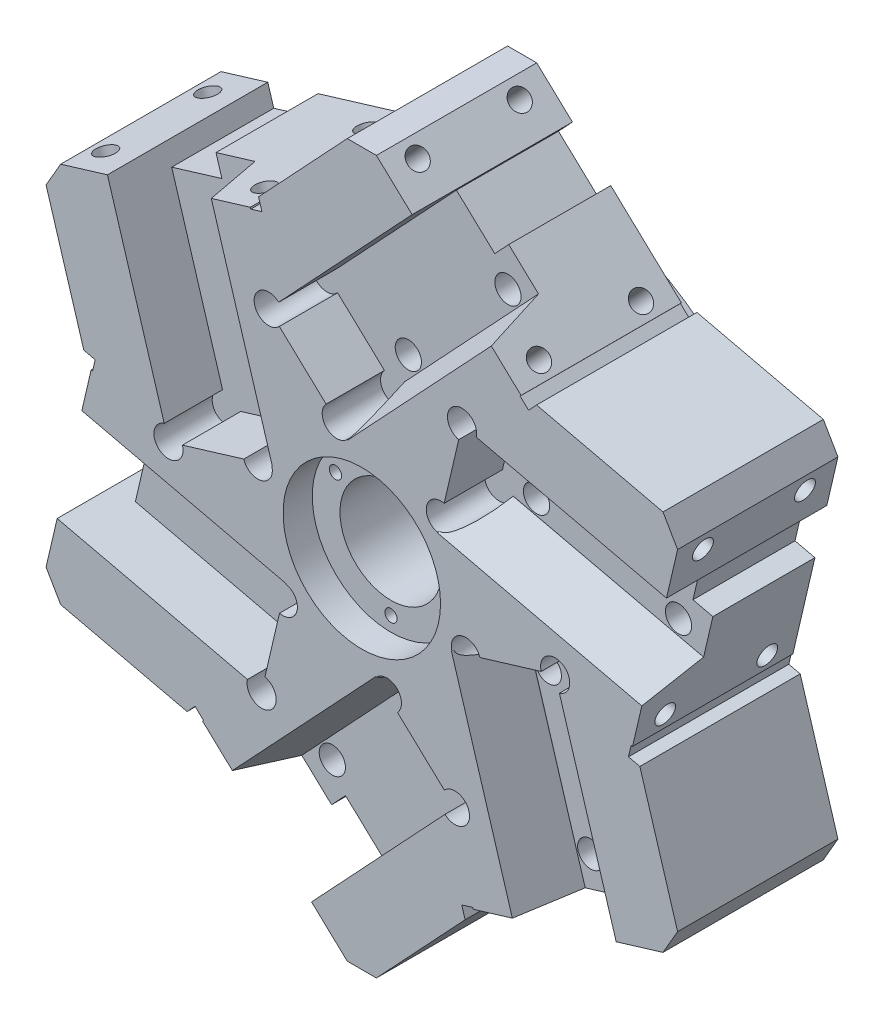
SolidWorks part; units mm, degrees
material "201 Annealed Stainless Steel (SS)"
ref_plane "Front" through (0, 0, 0) normal (0, 0, 1) x (1, 0, 0)
ref_plane "Top" through (0, 0, 0) normal (0, 1, 0) x (1, 0, 0)
ref_plane "Right" through (0, 0, 0) normal (1, 0, 0) x (0, 0, -1)
sketch "Sketch3" plane through (0, 0, 0) normal (0, 0, 1) x (1, 0, 0)
  line L0 (0, 0) -> (-108.311, 0) construction
  line L1 (-5, 122.18) -> (-108.311, 62.5334)
  line L2 (-108.311, 62.5334) -> (-108.311, -62.5334)
  line L3 (-108.311, -62.5334) -> (-5, -122.18)
  line L4 (5, -122.18) -> (103.311, -65.4201)
  line L5 (108.311, -56.7599) -> (108.311, 62.5334)
  line L6 (108.311, 62.5334) -> (5, 122.18)
  line L7 (0, 0) -> (0, 70.7448) construction
  line L8 (5, 122.18) -> (-5, 122.18)
  line L9 (5, -122.18) -> (-5, -122.18)
  line L10 (108.311, 56.7599) -> (103.311, 65.4201)
  line L11 (103.311, -65.4201) -> (108.311, -56.7599)
  line L12 (-5, -122.18) -> (5, -122.18)
  line L13 (-108.311, -56.7599) -> (-103.311, -65.4201)
  line L14 (-103.311, 65.4201) -> (-108.311, 56.7599)
  circle A0 centre (0, 0) radius 108.311 construction
  dimension "D1" = 244.36
  dimension "D2" = 10
  dimension "D3" = 10
  dimension "D4" = 6
extrude "Boss-Extrude1" add sketch "Sketch3" along normal blind 55 contours L1 L14 L2 L13 L3 L9 L4 L11 L5 L10 L6 L8 region at (0, 0, 0)
sketch "Sketch4" plane through (0, 0, 55) normal (0, 0, 1) x (1, 0, 0)
  line L0 (-5, 122.18) -> (-35.4257, 89.6654)
  line L2 (-103.311, 65.4201) -> (-38.2377, 85.1551)
  line L3 (-38.2377, 85.1551) -> (-38.0926, 84.6767)
  line L4 (-38.0926, 84.6767) -> (-34.2648, 85.8375)
  line L5 (-34.2648, 85.8375) -> (-35.4257, 89.6654)
  line L7 (-5, 122.18) -> (-59.1815, 172.8805)
  line L8 (-59.1815, 172.8805) -> (-103.311, 65.4201)
  line L9 (103.311, 65.4201) -> (59.9397, 75.5122)
  line L10 (103.311, 65.4201) -> (120.1282, 137.6929)
  line L11 (120.1282, 137.6929) -> (5, 122.18)
  line L12 (5, 122.18) -> (54.6277, 75.6924)
  line L13 (54.6277, 75.6924) -> (54.2858, 75.3275)
  line L14 (54.2858, 75.3275) -> (57.2051, 72.5929)
  line L15 (57.2051, 72.5929) -> (59.9397, 75.5122)
  line L16 (108.311, -56.7599) -> (95.3653, -14.1532)
  line L17 (108.311, -56.7599) -> (179.3096, -35.1876)
  line L18 (179.3096, -35.1876) -> (108.311, 56.7599)
  line L19 (108.311, 56.7599) -> (92.8654, -9.4627)
  line L20 (92.8654, -9.4627) -> (92.3784, -9.3492)
  line L21 (92.3784, -9.3492) -> (91.4699, -13.2446)
  line L22 (91.4699, -13.2446) -> (95.3653, -14.1532)
  line L23 (5, -122.18) -> (35.4257, -89.6654)
  line L24 (5, -122.18) -> (59.1815, -172.8805)
  line L25 (59.1815, -172.8805) -> (103.311, -65.4201)
  line L26 (103.311, -65.4201) -> (38.2377, -85.1551)
  line L27 (38.2377, -85.1551) -> (38.0926, -84.6767)
  line L28 (38.0926, -84.6767) -> (34.2648, -85.8375)
  line L29 (34.2648, -85.8375) -> (35.4257, -89.6654)
  line L30 (-103.311, -65.4201) -> (-59.9397, -75.5122)
  line L31 (-103.311, -65.4201) -> (-120.1282, -137.6929)
  line L32 (-120.1282, -137.6929) -> (-5, -122.18)
  line L33 (-5, -122.18) -> (-54.6277, -75.6924)
  line L34 (-54.6277, -75.6924) -> (-54.2858, -75.3275)
  line L35 (-54.2858, -75.3275) -> (-57.2051, -72.5929)
  line L36 (-57.2051, -72.5929) -> (-59.9397, -75.5122)
  line L37 (-108.311, 56.7599) -> (-95.3653, 14.1532)
  line L38 (-108.311, 56.7599) -> (-179.3096, 35.1876)
  line L39 (-179.3096, 35.1876) -> (-108.311, -56.7599)
  line L40 (-108.311, -56.7599) -> (-92.8654, 9.4627)
  line L41 (-92.8654, 9.4627) -> (-92.3784, 9.3492)
  line L42 (-92.3784, 9.3492) -> (-91.4699, 13.2446)
  line L43 (-91.4699, 13.2446) -> (-95.3653, 14.1532)
  line L45 (3, 19.5) -> (-3, 19.5)
  line L46 (3, 19.5) -> (3, 17.2409)
  line L48 (-3, 19.5) -> (-3, 17.2409)
  arc A0 (-3, 17.2409) -> (3, 17.2409) centre (0, 0) ccw
  point P52 (0, 19.5)
  dimension "D8" = 35
  dimension "D1" = 44.53
  dimension "D2" = 0.5
  dimension "D3" = 4
  dimension "D4" = 4
  dimension "D5" = 68
  dimension "D6" = 116.1686
  dimension "D9" = 6
  dimension "D10" = 2
  dimension "D7" = 6
extrude "Cut-Extrude2" cut sketch "Sketch4" against normal blind 141
sketch "Sketch5" plane through (0, 0, 55) normal (0, 0, 1) x (1, 0, 0)
  line L0 (-87.2549, 70.2895) -> (-67.7768, 6.1833)
  line L1 (-103.311, 65.4201) -> (-38.2377, 85.1551) construction
  line L2 (-61.5384, 2.8504) -> (-40.4853, 9.2352)
  line L3 (-37.1541, 15.4704) -> (-56.6321, 79.5766)
  line L4 (-95.3653, 14.1532) -> (-108.311, 56.7599) construction
  line L5 (-56.6321, 79.5766) -> (-87.2549, 70.2895)
  line L6 (-37.1541, 15.4704) -> (-35.7005, 10.6863) construction
  line L7 (-35.7005, 10.6863) -> (-40.4853, 9.2352) construction
  line L8 (-67.7768, 6.1833) -> (-66.3232, 1.3993) construction
  line L9 (-66.3232, 1.3993) -> (-61.5384, 2.8504) construction
  line L10 (-5.1793, 39.9116) -> (40.5993, 88.8332)
  line L11 (40.5993, 88.8332) -> (17.2451, 110.7097)
  line L12 (17.2451, 110.7097) -> (-28.5335, 61.7881)
  line L13 (-28.3007, 54.719) -> (-12.2447, 39.6789)
  line L14 (31.9748, 24.4412) -> (97.2314, 9.2566)
  line L15 (97.2314, 9.2566) -> (104.4999, 40.4202)
  line L16 (104.4999, 40.4202) -> (39.2433, 55.6047)
  line L17 (33.2377, 51.8686) -> (28.2406, 30.4437)
  line L18 (37.1541, -15.4704) -> (56.6321, -79.5766)
  line L19 (56.6321, -79.5766) -> (87.2549, -70.2895)
  line L20 (87.2549, -70.2895) -> (67.7768, -6.1833)
  line L21 (61.5384, -2.8504) -> (40.4853, -9.2352)
  line L22 (5.1793, -39.9116) -> (-40.5993, -88.8332)
  line L23 (-40.5993, -88.8332) -> (-17.2451, -110.7097)
  line L24 (-17.2451, -110.7097) -> (28.5335, -61.7881)
  line L25 (28.3007, -54.719) -> (12.2447, -39.6789)
  line L26 (-31.9748, -24.4412) -> (-97.2314, -9.2566)
  line L27 (-97.2314, -9.2566) -> (-104.4999, -40.4202)
  line L28 (-104.4999, -40.4202) -> (-39.2433, -55.6047)
  line L29 (-33.2377, -51.8686) -> (-28.2406, -30.4437)
  line L30 (5, 122.18) -> (54.6277, 75.6924) construction
  line L31 (-35.4257, 89.6654) -> (-5, 122.18) construction
  arc A0 (-67.7768, 6.1833) -> (-61.5384, 2.8504) centre (-66.3232, 1.3993) ccw
  arc A1 (-40.4853, 9.2352) -> (-37.1541, 15.4704) centre (-35.7005, 10.6863) ccw
  arc A2 (-12.2447, 39.6789) -> (-5.1793, 39.9116) centre (-8.5956, 36.2607) ccw
  arc A3 (-28.5335, 61.7881) -> (-28.3007, 54.719) centre (-31.9498, 58.1372) ccw
  arc A4 (28.2406, 30.4437) -> (31.9748, 24.4412) centre (27.1049, 25.5743) ccw
  arc A5 (39.2433, 55.6047) -> (33.2377, 51.8686) centre (34.3734, 56.7379) ccw
  arc A6 (40.4853, -9.2352) -> (37.1541, -15.4704) centre (35.7005, -10.6863) ccw
  arc A7 (67.7768, -6.1833) -> (61.5384, -2.8504) centre (66.3232, -1.3993) ccw
  arc A8 (12.2447, -39.6789) -> (5.1793, -39.9116) centre (8.5956, -36.2607) ccw
  arc A9 (28.5335, -61.7881) -> (28.3007, -54.719) centre (31.9498, -58.1372) ccw
  arc A10 (-28.2406, -30.4437) -> (-31.9748, -24.4412) centre (-27.1049, -25.5743) ccw
  arc A11 (-39.2433, -55.6047) -> (-33.2377, -51.8686) centre (-34.3734, -56.7379) ccw
  dimension "D4" = 10
  dimension "D1" = 24.08
  dimension "D2" = 32
  dimension "D3" = 72
  dimension "D6" = 24.08
  dimension "D5" = 6
extrude "Cut-Extrude3" cut sketch "Sketch5" against normal blind 20
sketch "Sketch6" plane through (-26.8708, 88.6024, 0) normal (-0.2902, 0.957, 0) x (0.957, 0.2902, 0)
  line L0 (-31.0999, -35) -> (-25.8782, -55)
  line L1 (-31.0999, -55) -> (-11.8782, -55) construction
  line L2 (-31.0999, -35) -> (-38.7766, -61.1303)
  line L3 (-38.7766, -61.1303) -> (-25.8782, -55)
  dimension "D1" = 14
  dimension "D2" = 48.207
  dimension "D3" = 27.2346
extrude "Cut-Extrude4" cut sketch "Sketch6" against normal blind 72
sketch "Sketch7" plane through (0, 0, 55) normal (0, 0, 1) x (1, 0, 0)
  circle A0 centre (0, 0) radius 27
  dimension "D1" = 54
extrude "Cut-Extrude7" cut sketch "Sketch7" against normal blind 10
pattern_circular "CirPattern5" count 6 every 60 about axis through (0, 0, 45) along (0, 0, -1) of "Cut-Extrude4"
sketch "Sketch9" plane through (0, 0, 35) normal (0, 0, 1) x (1, 0, 0)
  line L0 (-87.2549, 70.2895) -> (-85.2171, 63.5829)
  line L1 (-87.2549, 70.2895) -> (-67.7768, 6.1833) construction
  line L2 (-85.2171, 63.5829) -> (-67.998, 68.8148)
  line L3 (-67.998, 68.8148) -> (-70.0296, 75.5135)
  line L4 (-56.6321, 79.5766) -> (-87.2549, 70.2895) construction
  line L5 (-70.0296, 75.5135) -> (-87.2549, 70.2895)
  dimension "D1" = 18
  dimension "D2" = 7
extrude "Cut-Extrude8" cut sketch "Sketch9" against normal through all
pattern_circular "CirPattern6" count 6 every 60 about axis through (0, 0, -86) along (0, 0, 1) of "Cut-Extrude8"
hole_wizard "M10x1.0 Tapped Hole1" positions "Sketch11" profile "Sketch10" tap size "M10x1.0" standard "ISO"
sketch "Sketch11" plane through (0, 0, 35) normal (0, 0, 1) x (1, 0, 0)
  line L0 (-56.6321, 79.5766) -> (-70.0296, 75.5135) construction
  line L1 (-87.2549, 70.2895) -> (-67.7768, 6.1833) construction
  line L2 (-58.5098, 68.5574) -> (-43.9739, 20.717) construction
  line L4 (-37.1541, 15.4704) -> (-56.6321, 79.5766) construction
  point P0 (-58.5098, 68.5574)
  point P9 (-43.9739, 20.717)
  dimension "D1" = 10
  dimension "D2" = 27
  dimension "D3" = 50
sketch "Sketch10" plane through (-58.5098, 68.5574, 35) normal (1, 0, 0) x (0, -1, 0)
  line L0 (0, 0) -> (0, 27.7039)
  line L1 (0, 27.7039) -> (4.5, 25)
  line L2 (4.5, 25) -> (4.5, 0)
  line L5 (4.5, 0) -> (0, 0)
  line L10 (0, 27.7039) -> (-4.5, 25) construction
  line L11 (0, -6.35) -> (0, 107.95) construction
  dimension "Tap Drill Dia." = 9
  dimension "Tap Drill Depth" = 25
  dimension "Drill Angle" = 118
cosmetic thread "Hole Thread1" parameters "D1"=20, "D2"=10
cosmetic thread "Hole Thread2" parameters "D1"=20, "D2"=10
pattern_circular "CirPattern7" count 6 every 60 about axis through (0, 0, 0) along (0, 0, 1) of "M10x1.0 Tapped Hole1"
hole_wizard "M8x1.0 Tapped Hole1" positions "Sketch13" profile "Sketch12" tap size "M8x1.0" standard "ISO"
sketch "Sketch13" plane through (-26.8708, 88.6024, 0) normal (-0.2902, 0.957, 0) x (-0.957, -0.2902, 0)
  line L0 (74.1764, 10) -> (17.1764, 10) construction
  line L2 (79.8782, 0) -> (63.0999, 0) construction
  line L3 (87.1764, 55) -> (87.1764, 0) construction
  line L4 (74.1764, 10) -> (74.1764, 45) construction
  line L6 (74.1764, 45) -> (17.1764, 45) construction
  point P0 (74.1764, 10)
  point P14 (17.1764, 10)
  point P23 (74.1764, 45)
  point P25 (17.1764, 45)
  dimension "D1" = 10
  dimension "D2" = 13
  dimension "D3" = 57
  dimension "D4" = 35
sketch "Sketch12" plane through (-97.8546, 67.0749, 10) normal (0, 0, 1) x (-0.957, -0.2902, 0)
  line L0 (0, 0) -> (0, 22.103)
  line L1 (0, 22.103) -> (3.5, 20)
  line L2 (3.5, 20) -> (3.5, 0)
  line L5 (3.5, 0) -> (0, 0)
  line L10 (0, 22.103) -> (-3.5, 20) construction
  line L11 (0, -6.35) -> (0, 107.95) construction
  dimension "Tap Drill Dia." = 7
  dimension "Tap Drill Depth" = 20
  dimension "Drill Angle" = 118
cosmetic thread "Hole Thread3" parameters "D1"=19, "D2"=8
cosmetic thread "Hole Thread4" parameters "D1"=19, "D2"=8
cosmetic thread "Hole Thread5" parameters "D1"=19, "D2"=8
cosmetic thread "Hole Thread6" parameters "D1"=19, "D2"=8
pattern_circular "CirPattern8" count 6 every 60 about axis through (0, 0, -86) along (0, 0, 1) of "M8x1.0 Tapped Hole1"
hole_wizard "M5 Tapped Hole1" positions "Sketch15" profile "Sketch14" tap size "M5" standard "ISO"
sketch "Sketch15" plane through (0, 0, 45) normal (0, 0, 1) x (1, 0, 0)
  circle A0 centre (0, 0) radius 22 construction
  point P0 (0, -22)
  dimension "D1" = 44
sketch "Sketch14" plane through (0, -22, 45) normal (1, 0, 0) x (0, -1, 0)
  line L0 (0, 0) -> (0, 26.2618)
  line L1 (0, 26.2618) -> (2.1, 25)
  line L2 (2.1, 25) -> (2.1, 0)
  line L5 (2.1, 0) -> (0, 0)
  line L10 (0, 26.2618) -> (-2.1, 25) construction
  line L11 (0, -6.35) -> (0, 107.95) construction
  dimension "Tap Drill Dia." = 4.2
  dimension "Tap Drill Depth" = 25
  dimension "Drill Angle" = 118
cosmetic thread "Hole Thread7" parameters "D1"=24, "D2"=5
pattern_circular "CirPattern9" count 3 every 120 about axis through (0, 0, 0) along (0, 0, 1) of "M5 Tapped Hole1"
sketch "Sketch16" plane through (0, 0, 0) normal (0, 0, -1) x (-1, 0, 0)
  circle A0 centre (0, 0) radius 76
  circle A1 centre (0, 0) radius 78.5
  dimension "D1" = 2.5
  dimension "D2" = 152
extrude "Boss-Extrude2" add sketch "Sketch16" along normal blind 5
sketch "Sketch17" plane through (0, 0, -5) normal (0, 0, -1) x (-1, 0, 0)
  circle A0 centre (0, 0) radius 76
  circle A1 centre (0, 0) radius 76 construction
  circle A2 centre (0, 0) radius 81
  dimension "D1" = 5
extrude "Boss-Extrude3" add sketch "Sketch17" along normal blind 5
sketch "Sketch18" plane through (0, 0, 0) normal (0, 0, -1) x (-1, 0, 0)
  circle A0 centre (0, 0) radius 56
  dimension "D1" = 112
extrude "Cut-Extrude9" cut sketch "Sketch18" against normal blind 1.5
sketch "Sketch19" plane through (0, 0, 1.5) normal (0, 0, -1) x (-1, 0, 0)
  circle A0 centre (0, 0) radius 35
  dimension "D1" = 70
extrude "Cut-Extrude10" cut sketch "Sketch19" against normal blind 5.5
sketch "Sketch20" plane through (0, 0, 1.5) normal (0, 0, -1) x (-1, 0, 0)
  line L0 (0, 0) -> (0, 56) construction
  line L2 (3, 55.9196) -> (3, 34.8712)
  line L4 (-3, 55.9196) -> (-3, 34.8712)
  arc A0 (3, 55.9196) -> (-3, 55.9196) centre (0, 0) ccw
  arc A1 (3, 34.8712) -> (-3, 34.8712) centre (0, 0) ccw
  circle A2 centre (0, 0) radius 35 construction
  circle A3 centre (0, 0) radius 56 construction
  dimension "D1" = 6
extrude "Cut-Extrude11" cut sketch "Sketch20" against normal blind 5.5
ref_plane "Plane1" through (0, 31.5, 0) normal (0, -1, 0) x (1, 0, 0)
sketch "Sketch22" plane through (0, 31.5, 0) normal (0, -1, 0) x (1, 0, 0)
  line L0 (-9, 1.5) -> (-3, 7)
  line L1 (-3, 7) -> (-3, 1.5) construction
  line L2 (-35, 7) -> (35, 7) construction
  line L3 (-35, 1.5) -> (35, 1.5) construction
  line L4 (3, 7) -> (3, 1.5) construction
  line L5 (-9, 1.5) -> (-0.4411, 0)
  line L6 (-0.4411, 0) -> (-3, 7)
  dimension "D1" = 12
  dimension "D2" = 8.6893
  dimension "D3" = 59.979
extrude "Cut-Extrude13" cut sketch "Sketch22" along direction (0, -1, 0) on the side against the normal up to surface (24.4196 mm away) up to face at (0, 27.9598, 4.25)
pattern_circular "CirPattern10" count 6 every 60 about axis through (0, 0, 7) along (0, 0, 1) of "Cut-Extrude11"
pattern_circular "CirPattern11" count 6 every 60 about axis through (0, 0, 7) along (0, 0, 1) of "Cut-Extrude13"
hole_wizard "CBORE for M6 Hex Socket Head Cap Screw1" positions "Sketch27" profile "Sketch28" counterbore size "M6" standard "ISO"
sketch "Sketch27" plane through (0, 0, 1.5) normal (0, 0, -1) x (-1, 0, 0)
  line L5 (-22.475, 38.9278) -> (22.475, -38.9278) construction
  line L7 (-44.95, 0) -> (44.95, 0) construction
  arc A0 (-3, 34.8712) -> (-28.6993, 20.0337) centre (0, 0) ccw construction
  arc A4 (-31.6993, 14.8375) -> (-31.6993, -14.8375) centre (0, 0) ccw construction
  point P0 (-22.475, 38.9278)
  point P23 (-44.95, 0)
  point P25 (44.95, 0)
  point P27 (22.475, -38.9278)
  dimension "D1" = 9.95
  dimension "D2" = 9.95
  dimension "D3" = 60
sketch "Sketch28" plane through (22.475, 38.9278, 1.5) normal (1, 0, 0) x (0, 1, 0)
  line L0 (0, 0) -> (0, 21.9828)
  line L1 (0, 21.9828) -> (3.3, 20)
  line L2 (3.3, 20) -> (3.3, 6)
  line L3 (3.3, 6) -> (5.5, 6)
  line L4 (5.5, 6) -> (5.5, 0)
  line L5 (5.5, 0) -> (0, 0)
  line L10 (0, 21.9828) -> (-3.3, 20) construction
  line L11 (0, -6.35) -> (0, 107.95) construction
  dimension "Hole Dia." = 6.6
  dimension "Hole Depth" = 20
  dimension "C'Bore Dia." = 11
  dimension "C'Bore Depth" = 6
  dimension "Drill Angle" = 118
sketch "Sketch29" plane through (0, 0, 1.5) normal (0, 0, -1) x (-1, 0, 0)
  line L0 (19.75, 34.208) -> (-19.75, -34.208) construction
  line L1 (0, 0) -> (24.5596, 0) construction
  circle A0 centre (19.75, 34.208) radius 2.5
  circle A1 centre (-19.75, -34.208) radius 2.5
  arc A2 (28.6993, 20.0337) -> (3, 34.8712) centre (0, 0) ccw construction
  dimension "D2" = 5
  dimension "D3" = 2
  dimension "D1" = 60
extrude "Cut-Extrude14" cut sketch "Sketch29" against normal blind 10
sketch "Sketch30" plane through (0, 0, 0) normal (0, 0, -1) x (-1, 0, 0)
  line L0 (0, 0) -> (-62, 0) construction
  circle A0 centre (-62, 0) radius 4
  arc A1 (-49.9278, 25.3617) -> (-52.367, -19.8418) centre (0, 0) ccw construction
  dimension "D1" = 2
  dimension "D2" = 8
extrude "Cut-Extrude15" cut sketch "Sketch30" against normal blind 12
pattern_circular "CirPattern12" count 6 every 60 about axis through (0, 0, 7) along (0, 0, 1) of "Cut-Extrude15"
sketch "Sketch31" plane through (0, 0, 0) normal (0, 0, -1) x (-1, 0, 0)
  line L0 (0, 0) -> (0, 76) construction
  line L1 (0, 0) -> (4.3515, 75.8753) construction
  line L2 (0, 0) -> (-4.1485, 75.8867) construction
  line L3 (4.3515, 75.8753) -> (3.8362, 66.8901)
  line L5 (0, 0) -> (6.8451, 75.6911) construction
  line L6 (0, 0) -> (9.3312, 75.425) construction
  line L7 (9.3312, 75.425) -> (8.2262, 66.4931)
  arc A0 (9.3312, 75.425) -> (4.3515, 75.8753) centre (0, 0) ccw
  arc A1 (8.2262, 66.4931) -> (3.8362, 66.8901) centre (0, 0) ccw
  circle A2 centre (0, 0) radius 76 construction
  dimension "D1" = 134
  dimension "D2" = 8.5
  dimension "D3" = 4.15
  dimension "D4" = 2.5
extrude "Boss-Extrude4" add sketch "Sketch31" along normal blind 7 draft 14
pattern_circular "CirPattern13" count 70 every 5.143 about axis through (0, 0, 0) along (0, 0, -1) of "Boss-Extrude4"
